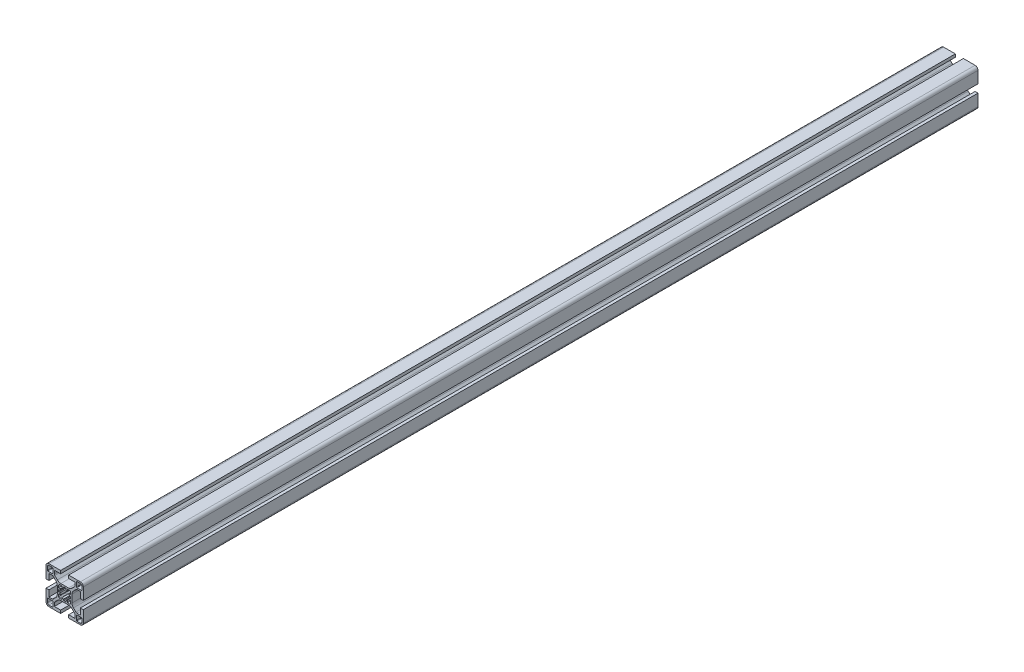
SolidWorks part; units mm, degrees
ref_plane "Front Plane" through (0, 0, 0) normal (0, 0, 1) x (1, 0, 0)
ref_plane "Top Plane" through (0, 0, 0) normal (0, 1, 0) x (1, 0, 0)
ref_plane "Right Plane" through (0, 0, 0) normal (1, 0, 0) x (0, 0, -1)
sketch "Sketch1" plane through (0, 0, 0) normal (0, 0, 1) x (1, 0, 0)
  line L0 (-19.05, -4.1) -> (-19.05, -16.05)
  line L1 (-16.05, -19.05) -> (-4.1, -19.05)
  line L2 (-4.1, -19.05) -> (-4.1, -16.05)
  line L3 (-4.1, -16.05) -> (-10.5, -16.05)
  line L4 (-10.5, -16.05) -> (-10.5, -12.7127)
  line L5 (-10.0313, -11.5814) -> (-7.4645, -9.0145)
  line L6 (-3.9289, -7.55) -> (3.9289, -7.55)
  line L7 (7.4645, -9.0145) -> (10.0313, -11.5814)
  line L8 (10.5, -12.7127) -> (10.5, -16.05)
  line L9 (10.5, -16.05) -> (4.1, -16.05)
  line L10 (4.1, -16.05) -> (4.1, -19.05)
  line L11 (4.1, -19.05) -> (16.05, -19.05)
  line L12 (19.05, -16.05) -> (19.05, -4.1)
  line L13 (19.05, -4.1) -> (16.05, -4.1)
  line L14 (16.05, -4.1) -> (16.05, -10.5)
  line L15 (16.05, -10.5) -> (12.7127, -10.5)
  line L16 (11.5814, -10.0313) -> (9.0145, -7.4645)
  line L17 (7.55, -3.9289) -> (7.55, 3.9289)
  line L18 (9.0145, 7.4645) -> (11.5814, 10.0313)
  line L19 (12.7127, 10.5) -> (16.05, 10.5)
  line L20 (16.05, 10.5) -> (16.05, 4.1)
  line L21 (16.05, 4.1) -> (19.05, 4.1)
  line L22 (19.05, 4.1) -> (19.05, 16.05)
  line L23 (16.05, 19.05) -> (4.1, 19.05)
  line L24 (4.1, 19.05) -> (4.1, 16.05)
  line L25 (4.1, 16.05) -> (10.5, 16.05)
  line L26 (10.5, 16.05) -> (10.5, 12.7127)
  line L27 (10.0313, 11.5814) -> (7.4645, 9.0145)
  line L28 (3.9289, 7.55) -> (-3.9289, 7.55)
  line L29 (-7.4645, 9.0145) -> (-10.0313, 11.5814)
  line L30 (-10.5, 12.7127) -> (-10.5, 16.05)
  line L31 (-10.5, 16.05) -> (-4.1, 16.05)
  line L32 (-4.1, 16.05) -> (-4.1, 19.05)
  line L33 (-4.1, 19.05) -> (-16.05, 19.05)
  line L34 (-19.05, 16.05) -> (-19.05, 4.1)
  line L35 (-19.05, 4.1) -> (-16.05, 4.1)
  line L36 (-16.05, 4.1) -> (-16.05, 10.5)
  line L37 (-16.05, 10.5) -> (-12.7127, 10.5)
  line L38 (-11.5814, 10.0313) -> (-9.0145, 7.4645)
  line L39 (-7.55, 3.9289) -> (-7.55, -3.9289)
  line L40 (-9.0145, -7.4645) -> (-11.5814, -10.0313)
  line L41 (-12.7127, -10.5) -> (-16.05, -10.5)
  line L42 (-16.05, -10.5) -> (-16.05, -4.1)
  line L43 (-16.05, -4.1) -> (-19.05, -4.1)
  arc A0 (-19.05, -16.05) -> (-16.05, -19.05) centre (-16.05, -16.05) ccw
  arc A1 (-10.5, -12.7127) -> (-10.0313, -11.5814) centre (-8.9002, -12.7127) cw
  arc A2 (-7.4645, -9.0145) -> (-3.9289, -7.55) centre (-3.9289, -12.55) cw
  arc A3 (3.9289, -7.55) -> (7.4645, -9.0145) centre (3.9289, -12.55) cw
  arc A4 (10.0313, -11.5814) -> (10.5, -12.7127) centre (8.9002, -12.7127) cw
  arc A5 (16.05, -19.05) -> (19.05, -16.05) centre (16.05, -16.05) ccw
  arc A6 (12.7127, -10.5) -> (11.5814, -10.0313) centre (12.7127, -8.9002) cw
  arc A7 (9.0145, -7.4645) -> (7.55, -3.9289) centre (12.55, -3.9289) cw
  arc A8 (7.55, 3.9289) -> (9.0145, 7.4645) centre (12.55, 3.9289) cw
  arc A9 (11.5814, 10.0313) -> (12.7127, 10.5) centre (12.7127, 8.9002) cw
  arc A10 (19.05, 16.05) -> (16.05, 19.05) centre (16.05, 16.05) ccw
  arc A11 (10.5, 12.7127) -> (10.0313, 11.5814) centre (8.9002, 12.7127) cw
  arc A12 (7.4645, 9.0145) -> (3.9289, 7.55) centre (3.9289, 12.55) cw
  arc A13 (-3.9289, 7.55) -> (-7.4645, 9.0145) centre (-3.9289, 12.55) cw
  arc A14 (-10.0313, 11.5814) -> (-10.5, 12.7127) centre (-8.9002, 12.7127) cw
  arc A15 (-16.05, 19.05) -> (-19.05, 16.05) centre (-16.05, 16.05) ccw
  arc A16 (-12.7127, 10.5) -> (-11.5814, 10.0313) centre (-12.7127, 8.9002) cw
  arc A17 (-9.0145, 7.4645) -> (-7.55, 3.9289) centre (-12.55, 3.9289) cw
  arc A18 (-7.55, -3.9289) -> (-9.0145, -7.4645) centre (-12.55, -3.9289) cw
  arc A19 (-11.5814, -10.0313) -> (-12.7127, -10.5) centre (-12.7127, -8.9002) cw
  circle A20 centre (0, 0) radius 5
extrude "Boss-Extrude1" add sketch "Sketch1" against normal blind 914.4
sketch "Sketch2" plane through (0, 0, 0) normal (0, 0, 1) x (1, 0, 0)
  line L0 (-17.55, -12.5) -> (-17.55, -16.05)
  line L1 (-16.05, -17.55) -> (-12.5, -17.55)
  line L2 (-12, -17.05) -> (-12, -12.5)
  line L3 (-12.5, -12) -> (-17.05, -12)
  arc A0 (-17.55, -16.05) -> (-16.05, -17.55) centre (-16.05, -16.05) ccw
  arc A1 (-12.5, -17.55) -> (-12, -17.05) centre (-12.5, -17.05) ccw
  arc A2 (-12, -12.5) -> (-12.5, -12) centre (-12.5, -12.5) ccw
  arc A3 (-17.05, -12) -> (-17.55, -12.5) centre (-17.05, -12.5) ccw
sketch "Sketch3" plane through (0, 0, 0) normal (0, 0, 1) x (1, 0, 0)
  line L0 (12.5, -17.55) -> (16.05, -17.55)
  line L1 (17.55, -16.05) -> (17.55, -12.5)
  line L2 (17.05, -12) -> (12.5, -12)
  line L3 (12, -12.5) -> (12, -17.05)
  arc A0 (12, -17.05) -> (12.5, -17.55) centre (12.5, -17.05) ccw
  arc A1 (16.05, -17.55) -> (17.55, -16.05) centre (16.05, -16.05) ccw
  arc A2 (17.55, -12.5) -> (17.05, -12) centre (17.05, -12.5) ccw
  arc A3 (12.5, -12) -> (12, -12.5) centre (12.5, -12.5) ccw
sketch "Sketch4" plane through (0, 0, 0) normal (0, 0, 1) x (1, 0, 0)
  line L0 (-6.05, 1.0672) -> (-6.05, -1.191)
  line L1 (-6.05, -1.191) -> (-4.8565, -1.1891)
  line L2 (-4.2083, -2.7) -> (-6.05, -2.7)
  line L3 (-6.05, -2.7) -> (-6.05, -5.05)
  line L4 (-5.05, -6.05) -> (-2.7, -6.05)
  line L5 (-2.7, -6.05) -> (-2.7, -4.2083)
  line L6 (-1.15, -4.866) -> (-1.15, -6.05)
  line L7 (-1.15, -6.05) -> (1.15, -6.05)
  line L8 (1.15, -6.05) -> (1.15, -4.866)
  line L9 (2.7, -4.2083) -> (2.7, -6.05)
  line L10 (2.7, -6.05) -> (5.05, -6.05)
  line L11 (6.05, -5.05) -> (6.05, -2.7)
  line L12 (6.05, -2.7) -> (4.2083, -2.7)
  line L13 (4.8603, -1.1736) -> (6.05, -1.1717)
  line L14 (6.05, -1.1717) -> (6.05, 1.1063)
  line L15 (6.05, 1.1063) -> (4.8769, 1.1025)
  line L16 (4.2083, 2.7) -> (6.05, 2.7)
  line L17 (6.05, 2.7) -> (6.05, 5.05)
  line L18 (5.05, 6.05) -> (2.7, 6.05)
  line L19 (2.7, 6.05) -> (2.7, 4.2083)
  line L20 (1.15, 4.866) -> (1.15, 6.05)
  line L21 (1.15, 6.05) -> (-1.15, 6.05)
  line L22 (-1.15, 6.05) -> (-1.15, 4.866)
  line L23 (-2.7, 4.2083) -> (-2.7, 6.05)
  line L24 (-2.7, 6.05) -> (-5.05, 6.05)
  line L25 (-6.05, 5.05) -> (-6.05, 2.7)
  line L26 (-6.05, 2.7) -> (-4.2083, 2.7)
  line L27 (-4.8839, 1.071) -> (-6.05, 1.0672)
  arc A0 (-4.8565, -1.1891) -> (-4.2083, -2.7) centre (0, 0) ccw
  arc A1 (-6.05, -5.05) -> (-5.05, -6.05) centre (-5.05, -5.05) ccw
  arc A2 (-2.7, -4.2083) -> (-1.15, -4.866) centre (0, 0) ccw
  arc A3 (1.15, -4.866) -> (2.7, -4.2083) centre (0, 0) ccw
  arc A4 (5.05, -6.05) -> (6.05, -5.05) centre (5.05, -5.05) ccw
  arc A5 (4.2083, -2.7) -> (4.8603, -1.1736) centre (0, 0) ccw
  arc A6 (4.8769, 1.1025) -> (4.2083, 2.7) centre (0, 0) ccw
  arc A7 (6.05, 5.05) -> (5.05, 6.05) centre (5.05, 5.05) ccw
  arc A8 (2.7, 4.2083) -> (1.15, 4.866) centre (0, 0) ccw
  arc A9 (-1.15, 4.866) -> (-2.7, 4.2083) centre (0, 0) ccw
  arc A10 (-5.05, 6.05) -> (-6.05, 5.05) centre (-5.05, 5.05) ccw
  arc A11 (-4.2083, 2.7) -> (-4.8839, 1.071) centre (0, 0) ccw
sketch "Sketch5" plane through (0, 0, 0) normal (0, 0, 1) x (1, 0, 0)
  line L0 (12, 17.05) -> (12, 12.5)
  line L1 (12.5, 12) -> (17.05, 12)
  line L2 (17.55, 12.5) -> (17.55, 16.05)
  line L3 (16.05, 17.55) -> (12.5, 17.55)
  arc A0 (12, 12.5) -> (12.5, 12) centre (12.5, 12.5) ccw
  arc A1 (17.05, 12) -> (17.55, 12.5) centre (17.05, 12.5) ccw
  arc A2 (17.55, 16.05) -> (16.05, 17.55) centre (16.05, 16.05) ccw
  arc A3 (12.5, 17.55) -> (12, 17.05) centre (12.5, 17.05) ccw
sketch "Sketch6" plane through (0, 0, 0) normal (0, 0, 1) x (1, 0, 0)
  line L0 (-17.05, 12) -> (-12.5, 12)
  line L1 (-12, 12.5) -> (-12, 17.05)
  line L2 (-12.5, 17.55) -> (-16.05, 17.55)
  line L3 (-17.55, 16.05) -> (-17.55, 12.5)
  arc A0 (-17.55, 12.5) -> (-17.05, 12) centre (-17.05, 12.5) ccw
  arc A1 (-12.5, 12) -> (-12, 12.5) centre (-12.5, 12.5) ccw
  arc A2 (-12, 17.05) -> (-12.5, 17.55) centre (-12.5, 17.05) ccw
  arc A3 (-16.05, 17.55) -> (-17.55, 16.05) centre (-16.05, 16.05) ccw
extrude "Cut-Extrude1" cut sketch "Sketch2" against normal blind 6000
extrude "Cut-Extrude2" cut sketch "Sketch3" against normal blind 6000
extrude "Cut-Extrude3" cut sketch "Sketch4" against normal blind 6000
extrude "Cut-Extrude4" cut sketch "Sketch5" against normal blind 6000
extrude "Cut-Extrude5" cut sketch "Sketch6" against normal blind 6000
ref_plane "Plane1" through (0, 19.05, 0) normal (0, 1, 0) x (-1, 0, 0)
ref_plane "Plane2" through (0, -19.05, 0) normal (0, -1, 0) x (1, 0, 0)
ref_plane "Plane3" through (19.05, 0, 0) normal (1, 0, 0) x (0, 0, -1)
ref_plane "Plane4" through (-19.05, 0, 0) normal (-1, 0, 0) x (0, 0, 1)
ref_plane "Plane5" through (0, 0, 0) normal (0, 0, 1) x (1, 0, 0)
ref_plane "Plane6" through (0, 0, 0) normal (0, 0, 1) x (1, 0, 0)
ref_plane "Plane7" through (0, 0, 0) normal (0, 0, 1) x (1, 0, 0)
ref_plane "Plane8" through (0, 0, -50) normal (0, 0, 1) x (1, 0, 0)
ref_plane "Plane9" through (0, 0, -50) normal (0, 0, 1) x (1, 0, 0)
ref_plane "Plane10" through (0, 0, -50) normal (0, 0, 1) x (1, 0, 0)
ref_plane "side_4d XY" through (0, 0, 0) normal (0, 0, 1) x (1, 0, 0)
ref_plane "side_4d XZ" through (-19.05, 0, 0) normal (-1, 0, 0) x (0, 0, 1)
ref_plane "side_4d YZ" through (0, 0, 0) normal (0, -1, 0) x (1, 0, 0)
ref_axis "side_4d X" through (-19.05, 50, 0) along (0, -1, 0)
ref_axis "side_4d Y" through (-80.9, 0, 0) along (1, 0, 0)
ref_axis "side_4d Z" through (-19.05, 0, 50) along (0, 0, -1)
sketch3d "side_4d"
  point P0 (-19.05, 0, 0)
ref_plane "side_1a XY" through (0, 0, 0) normal (0, 0, 1) x (1, 0, 0)
ref_plane "side_1a XZ" through (0, 19.05, 0) normal (0, -1, 0) x (1, 0, 0)
ref_plane "side_1a YZ" through (0, 0, 0) normal (1, 0, 0) x (0, 0, -1)
ref_axis "side_1a X" through (-80.9, 19.05, 0) along (1, 0, 0)
ref_axis "side_1a Y" through (0, -50, 0) along (0, 1, 0)
ref_axis "side_1a Z" through (0, 19.05, 80.9) along (0, 0, -1)
sketch3d "side_1a"
  point P0 (0, 19.05, 0)
ref_plane "side_2b XY" through (0, 0, 0) normal (0, 0, 1) x (1, 0, 0)
ref_plane "side_2b XZ" through (19.05, 0, 0) normal (1, 0, 0) x (0, 0, -1)
ref_plane "side_2b YZ" through (0, 0, 0) normal (0, 1, 0) x (-1, 0, 0)
ref_axis "side_2b X" through (19.05, -50, 0) along (0, 1, 0)
ref_axis "side_2b Y" through (80.9, 0, 0) along (-1, 0, 0)
ref_axis "side_2b Z" through (19.05, 0, 50) along (0, 0, -1)
sketch3d "side_2b"
  point P0 (19.05, 0, 0)
ref_plane "side_3c XY" through (0, 0, 0) normal (0, 0, 1) x (1, 0, 0)
ref_plane "side_3c XZ" through (0, -19.05, 0) normal (0, 1, 0) x (-1, 0, 0)
ref_plane "side_3c YZ" through (0, 0, 0) normal (-1, 0, 0) x (0, 0, 1)
ref_axis "side_3c X" through (80.9, -19.05, 0) along (-1, 0, 0)
ref_axis "side_3c Y" through (0, 50, 0) along (0, -1, 0)
ref_axis "side_3c Z" through (0, -19.05, 80.9) along (0, 0, -1)
sketch3d "side_3c"
  point P0 (0, -19.05, 0)
ref_plane "start XY" through (0, 0, 0) normal (0, 0, 1) x (1, 0, 0)
ref_plane "start XZ" through (0, 0, 0) normal (0, -1, 0) x (1, 0, 0)
ref_plane "start YZ" through (0, 0, 0) normal (1, 0, 0) x (0, 0, -1)
ref_axis "start X" through (-80.9, 0, 0) along (1, 0, 0)
ref_axis "start Y" through (0, -50, 0) along (0, 1, 0)
ref_axis "start Z" through (0, 0, 80.9) along (0, 0, -1)
sketch3d "start"
  point P0 (0, 0, 0)
ref_plane "end XY" through (0, 0, -50) normal (0, 0, -1) x (-1, 0, 0)
ref_plane "end XZ" through (0, 0, 0) normal (0, 1, 0) x (-1, 0, 0)
ref_plane "end YZ" through (0, 0, 0) normal (1, 0, 0) x (0, 0, -1)
ref_axis "end X" through (-80.9, 0, -50) along (1, 0, 0)
ref_axis "end Y" through (0, 50, -50) along (0, -1, 0)
ref_axis "end Z" through (0, 0, -80.9) along (0, 0, 1)
sketch3d "end"
  point P0 (0, 0, -50)
sketch3d "BoreSketch-28-318"
  point P0 (-20.05, 0, -33)
  point P1 (-20.05, 0, -23)
  point P2 (-20.05, -10, -33)
ref_plane "BorePlane-28-349" through (-20.05, 0, 0) normal (1, 0, 0) x (0, 0, -1)
hole_wizard "" positions "Sketch8" profile "Sketch7" legacy
sketch "Sketch8" plane through (-20.05, 0, 0) normal (1, 0, 0) x (0, 0, -1)
  point P0 (33, 0)
sketch "Sketch7" plane through (-20.05, 0, -33) normal (0, 1, 0) x (0, 0, 1)
  line L0 (0, 0) -> (0, 25)
  line L1 (0, 25) -> (5.75, 25)
  line L2 (5.75, 25) -> (5.75, 24.85)
  line L3 (5.75, 24.85) -> (6.6, 24)
  line L4 (6.6, 24) -> (6.6, 0)
  line L5 (6.6, 0) -> (0, 0)
  line L6 (0, -6.13) -> (0, 109.2824) construction
  line L7 (-5.75, 24.85) -> (-6.6, 24) construction
  line L8 (0, 25) -> (-5.75, 25) construction
  dimension "Diameter" = 11.5
  dimension "Depth" = 25
  dimension "C-Drill Diameter" = 13.2
  dimension "C-Drill Depth" = 24
  dimension "C-Drill Angle" = 90
sketch3d "BoreSketch-28-458"
  point P0 (-20.05, 0, -500.4)
  point P1 (-20.05, 0, -490.4)
  point P2 (-20.05, -10, -500.4)
ref_plane "BorePlane-28-490" through (-20.05, 0, 0) normal (1, 0, 0) x (0, 0, -1)
hole_wizard "Hole2" positions "Sketch10" profile "Sketch9" legacy
sketch "Sketch10" plane through (-20.05, 0, 0) normal (1, 0, 0) x (0, 0, -1)
  point P0 (500.4, 0)
sketch "Sketch9" plane through (-20.05, 0, -500.4) normal (0, 1, 0) x (0, 0, 1)
  line L0 (0, 0) -> (0, 25)
  line L1 (0, 25) -> (5.75, 25)
  line L2 (5.75, 25) -> (5.75, 24.85)
  line L3 (5.75, 24.85) -> (6.6, 24)
  line L4 (6.6, 24) -> (6.6, 0)
  line L5 (6.6, 0) -> (0, 0)
  line L6 (0, -6.13) -> (0, 109.2824) construction
  line L7 (-5.75, 24.85) -> (-6.6, 24) construction
  line L8 (0, 25) -> (-5.75, 25) construction
  dimension "Diameter" = 11.5
  dimension "Depth" = 25
  dimension "C-Drill Diameter" = 13.2
  dimension "C-Drill Depth" = 24
  dimension "C-Drill Angle" = 90
